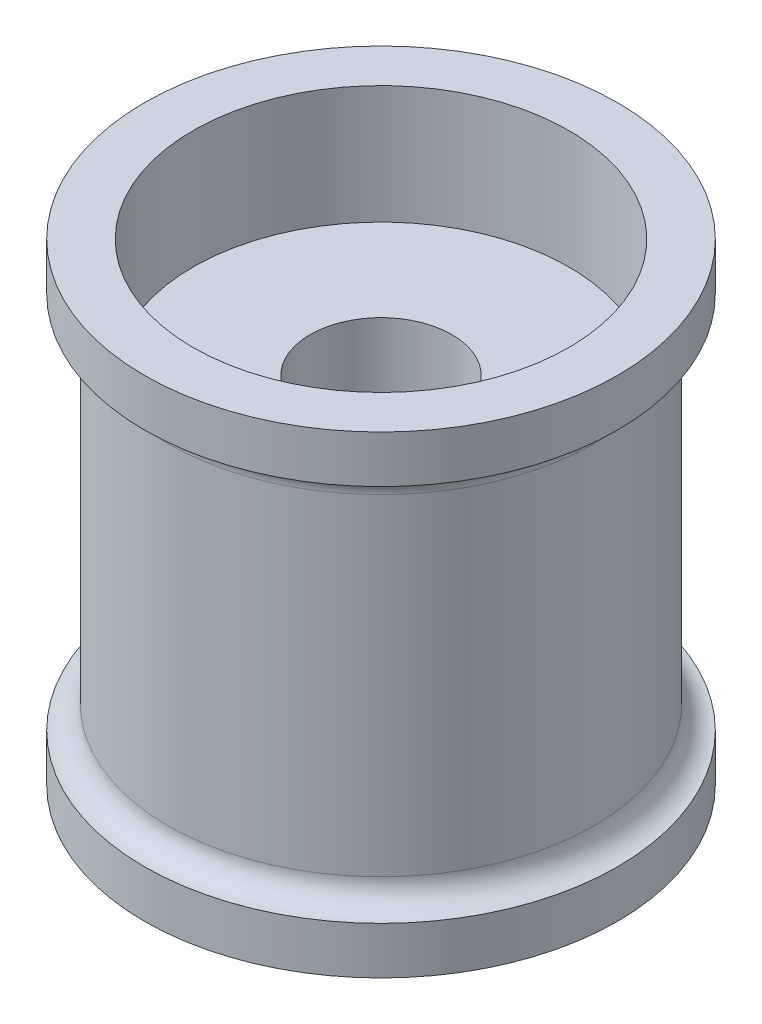
SolidWorks part; units mm, degrees
ref_plane "前视基准面" through (0, 0, 0) normal (0, 0, 1) x (1, 0, 0)
ref_plane "上视基准面" through (0, 0, 0) normal (0, 1, 0) x (1, 0, 0)
ref_plane "右视基准面" through (0, 0, 0) normal (1, 0, 0) x (0, 0, -1)
other "Configuration Table"
sketch "草图1" plane through (0, 0, 0) normal (0, 1, 0) x (1, 0, 0)
  circle A0 centre (0, 0) radius 8
  circle A1 centre (0, 0) radius 3
  dimension "D1" = 6
  dimension "D2" = 16
extrude "凸台-拉伸1" add sketch "草图1" along normal blind 20
sketch "草图2" plane through (0, 20, 0) normal (0, 1, 0) x (1, 0, 0)
  circle A0 centre (0, 0) radius 9
  circle A1 centre (0, 0) radius 3
  dimension "D1" = 18
extrude "凸台-拉伸2" add sketch "草图2" against normal blind 20
sketch "草图3" plane through (0, 20, 0) normal (0, 1, 0) x (1, 0, 0)
  circle A0 centre (0, 0) radius 9
  circle A1 centre (0, 0) radius 10
  dimension "D1" = 20
extrude "凸台-拉伸3" add sketch "草图3" against normal blind 2
ref_plane "基准面1" through (0, 10, 0) normal (0, -1, 0) x (-1, 0, 0)
mirror "镜向1" about plane through (0, 10, 0) normal (0, -1, 0) of "凸台-拉伸3"
fillet "圆角1" radius 1 1 edges at (0, 18, 9) type face fillet first side face at (0, 18, 9) second side face at (0, 18, 9)
fillet "圆角2" radius 1 1 edges at (0, 2, 9) type face fillet first side face at (0, 2, 10) second side face at (0, 17, 9)
sketch "草图4" plane through (0, 0, 0) normal (0, -1, 0) x (1, 0, 0)
  circle A0 centre (0, 0) radius 7.95
  dimension "D1" = 15.9
extrude "切除-拉伸1" cut sketch "草图4" against normal blind 5
sketch "草图5" plane through (0, 20, 0) normal (0, 1, 0) x (1, 0, 0)
  circle A0 centre (0, 0) radius 7.95
  dimension "D1" = 15.9
extrude "切除-拉伸2" cut sketch "草图5" against normal blind 5
